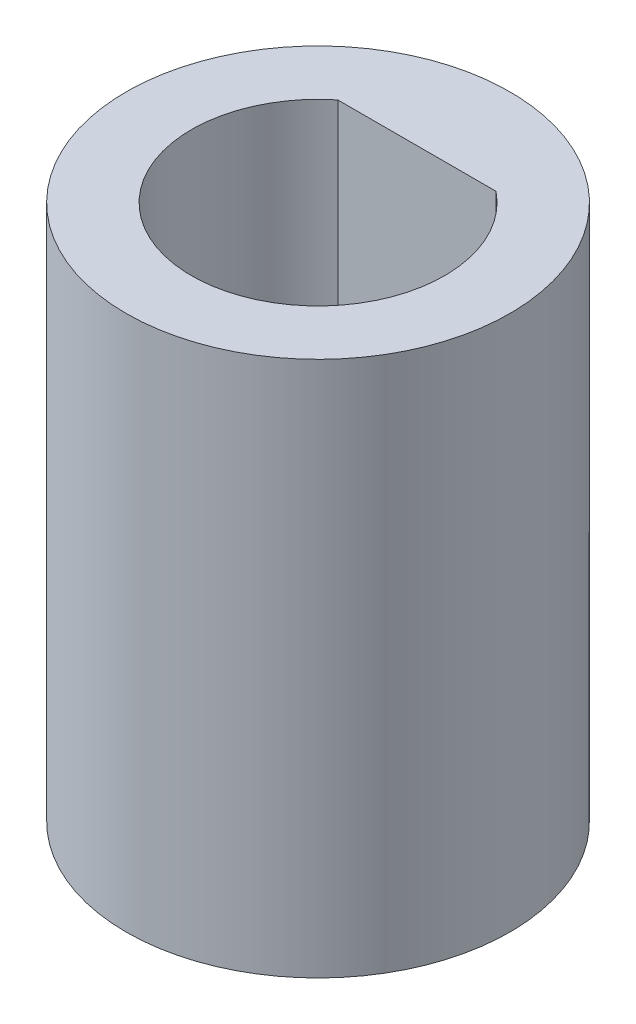
SolidWorks part; units mm, degrees
ref_plane "Front Plane" through (0, 0, 0) normal (0, 0, 1) x (1, 0, 0)
ref_plane "Top Plane" through (0, 0, 0) normal (0, 1, 0) x (1, 0, 0)
ref_plane "Right Plane" through (0, 0, 0) normal (1, 0, 0) x (0, 0, -1)
sketch "Sketch1" plane through (0, 0, 0) normal (0, 1, 0) x (1, 0, 0)
  line L0 (-2.4218, 3.025) -> (2.4218, 3.025) construction
  circle A0 centre (0, 0) radius 5.875
  circle A1 centre (0, 0) radius 3.875 construction
  arc A2 (-2.4218, 3.025) -> (2.4218, 3.025) centre (0, 0) ccw construction
  point P6 (0, -3.875)
  dimension "D1" = 7.75
  dimension "D2" = 2
  dimension "D3" = 6.9
extrude "Boss-Extrude1" add sketch "Sketch1" against normal blind 16.4
ref_plane "Plane1" through (0, 0, 0) normal (0, 1, 0) x (1, 0, 0)
ref_axis "Axis1" through (0, 1.27, 0) along (0, -1, 0)
sketch "Sketch2" plane through (0, 0, 0) normal (0, 0, 1) x (1, 0, 0)
  line L0 (5.6375, 0) -> (-5.6375, 0) construction
  circle A0 centre (0, -18.75) radius 18.75
  dimension "D1" = 37.5
sketch "Sketch3" plane through (0, 0, 0) normal (0, 1, 0) x (1, 0, 0)
  line L0 (-2.4218, 3.025) -> (2.4218, 3.025) construction
  line L1 (-2.4218, 3.025) -> (2.4218, 3.025)
  circle A0 centre (0, 0) radius 3.875 construction
  arc A1 (-2.4218, 3.025) -> (2.4218, 3.025) centre (0, 0) ccw
extrude "Cut-Extrude1" cut sketch "Sketch3" against normal through all
